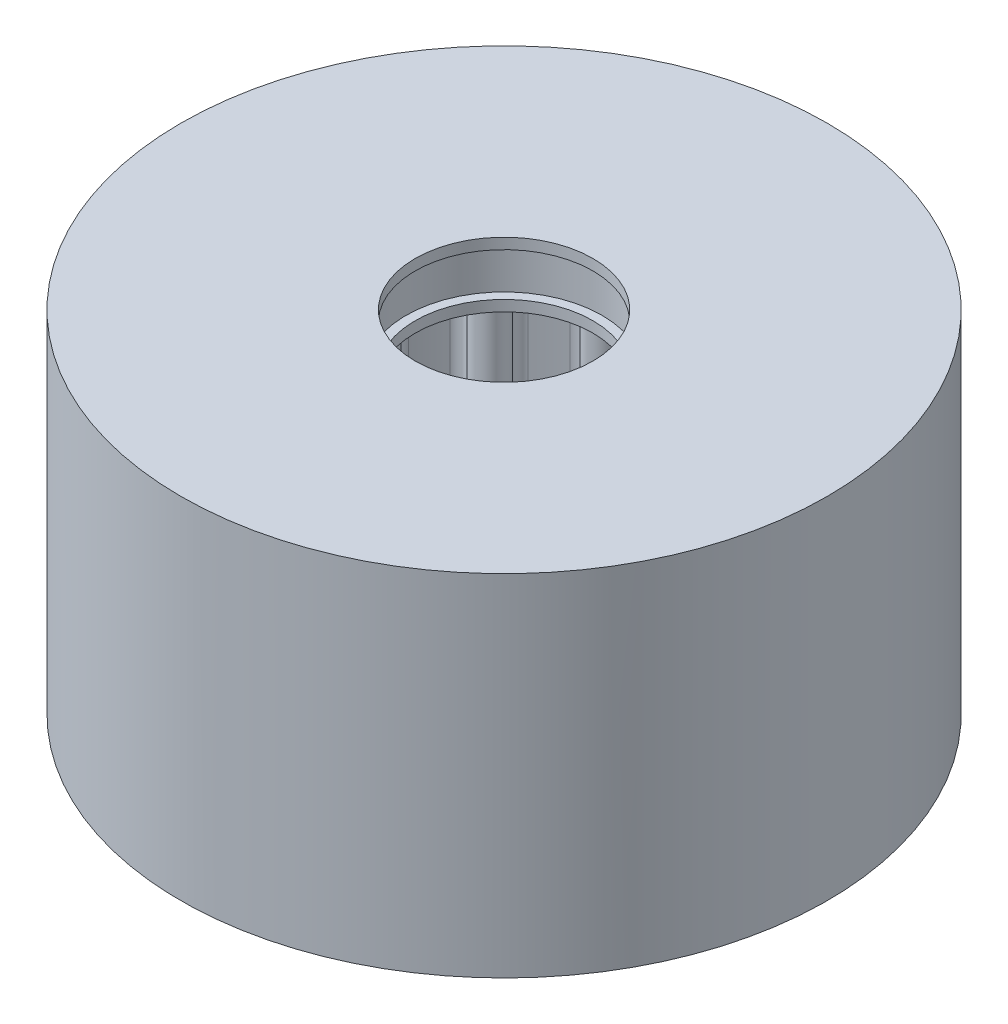
SolidWorks part; units mm, degrees
ref_plane "Front Plane" through (0, 0, 0) normal (0, 0, 1) x (1, 0, 0)
ref_plane "Top Plane" through (0, 0, 0) normal (0, 1, 0) x (1, 0, 0)
ref_plane "Right Plane" through (0, 0, 0) normal (1, 0, 0) x (0, 0, -1)
ref_axis "Housing Axis" through (0, 3.3, 0) along (0, -1, 0)
sketch "Sketch1" plane through (0, 0, 0) normal (0, 1, 0) x (1, 0, 0)
  line L0 (0, 0) -> (26.1689, 3.9443) construction
  line L1 (0, 0) -> (26.1689, -3.9443) construction
  line L2 (0, 0) -> (25, 0) construction
  line L3 (26.1689, 3.9443) -> (29.6649, 4.4713)
  line L4 (26.1689, -3.9443) -> (29.6649, -4.4713)
  circle A0 centre (0, 0) radius 25 construction
  arc A1 (25.2063, 1.4858) -> (25.2062, -1.4858) centre (25, 0) ccw
  arc A2 (26.1689, 3.9443) -> (26.339, 2.5735) centre (0, 0) cw
  arc A3 (26.339, -2.5735) -> (26.1689, -3.9443) centre (0, 0) cw
  arc A4 (25.2063, 1.4858) -> (26.339, 2.5735) centre (25.3438, 2.4763) ccw
  arc A5 (25.2062, -1.4858) -> (26.339, -2.5735) centre (25.3438, -2.4763) cw
  arc A6 (25.2063, 1.4858) -> (25.2063, -1.4858) centre (0, 0) cw construction
  arc A7 (29.6649, 4.4713) -> (29.6649, -4.4713) centre (0, 0) cw
  point P14 (26.4623, -0.3341)
  dimension "D1" = 50
  dimension "D2" = 3
  dimension "D5" = 1
  dimension "D6" = 30
  dimension "D3" = 17.143
  dimension "D4" = 0.25
extrude "Boss-Extrude1" add sketch "Sketch1" along normal mid plane 26.5
pattern_circular "CirPattern1" count 21 over 360 about axis through (0, 3.3, 0) along (0, -1, 0) of "Boss-Extrude1"
sketch "Sketch2" plane through (0, 13.25, 0) normal (0, 1, 0) x (1, 0, 0)
  circle A0 centre (0, 0) radius 30
  circle A1 centre (0, 0) radius 8.25
  circle A2 centre (0, 0) radius 30 construction
  dimension "D1" = 16.5
extrude "Boss-Extrude2" add sketch "Sketch2" along normal blind 6
ref_plane "Plane1" through (0, 16.25, 0) normal (0, -1, 0) x (-1, 0, 0)
sketch "Sketch3" plane through (0, 16.25, 0) normal (0, -1, 0) x (-1, 0, 0)
  circle A0 centre (0, 0) radius 9.1
  dimension "D1" = 18.2
extrude "Cut-Extrude1" cut sketch "Sketch3" against normal mid plane 4
equation "\"RotorRadius\"= 25mm"
equation "\"Eccentricity\"= 1.00mm"
equation "\"RollerRadius\"= 1.5mm"
equation "\"GearRatio\"= 20"
equation "\"RollerCount\"=\"GearRatio\" + 1"
equation "\"RotorThickness\"= 6mm"
equation "\"OutputRollerRadius\"= 2mm"
equation "\"OutputRollerCount\"= 6"
equation "\"OutputRollerHoleCircleRadius\"=\"RotorRadius\"- 4 * \"OutputRollerRadius\""
equation "\"RotorGap\"= 0.5mm"
equation "\"D1@Sketch1\"=\"RotorRadius\"*2"
equation "\"D2@Sketch1\"=2*\"RollerRadius\""
equation "\"rotorCount\" = 2"
equation "\"D1@Boss-Extrude1\"=(\"rotorCount\" + 2) * \"RotorThickness\" + 0.5mm * (\"rotorCount\" + 3)"
equation "\"D1@CirPattern1\"=\"GearRatio\"+1"
equation "\"D3@Sketch1\"=360deg/(\"GearRatio\" + 1)"
